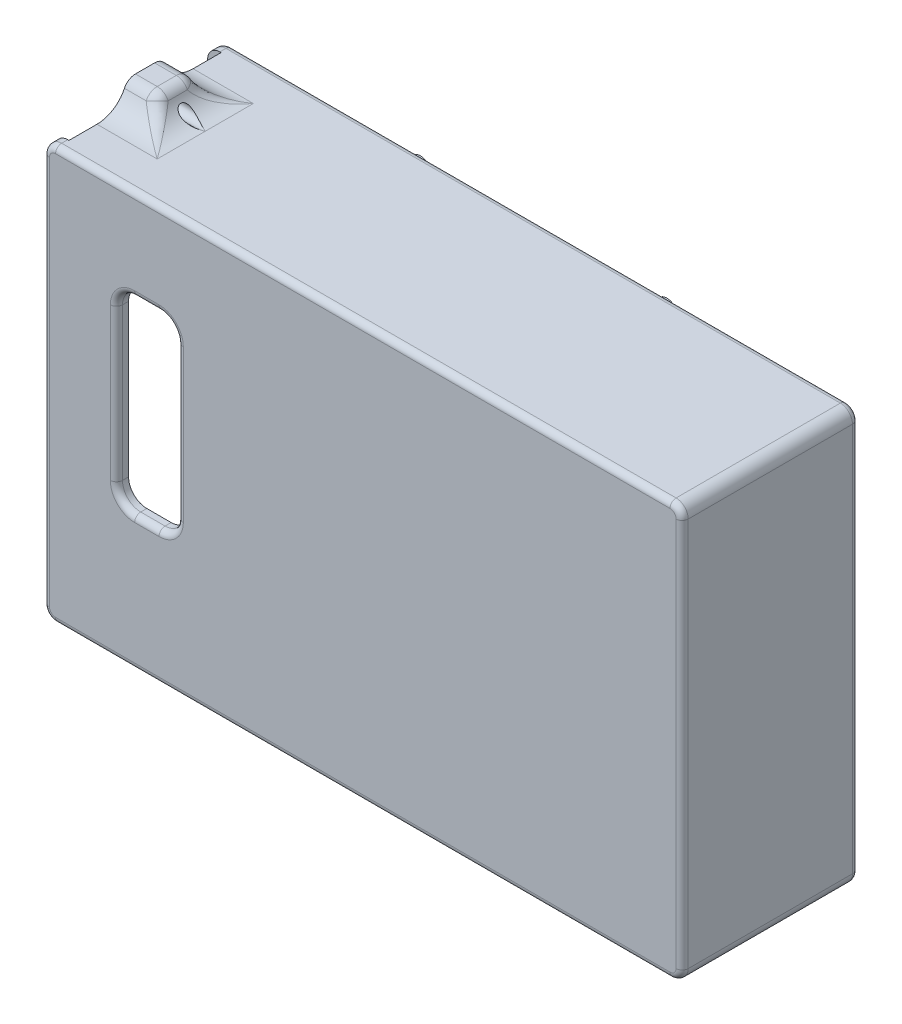
SolidWorks part; units mm, degrees
ref_plane "Front Plane" through (0, 0, 0) normal (0, 0, 1) x (1, 0, 0)
ref_plane "Top Plane" through (0, 0, 0) normal (0, 1, 0) x (1, 0, 0)
ref_plane "Right Plane" through (0, 0, 0) normal (1, 0, 0) x (0, 0, -1)
sketch "Sketch1" plane through (0, 0, 0) normal (0, 0, 1) x (1, 0, 0)
  line L0 (0, 0) -> (0, 68)
  line L1 (0, -55) -> (0, 55) construction
  line L2 (0, 68) -> (105, 68)
  line L3 (105, 68) -> (105, 0)
  line L4 (105, 0) -> (0, 0)
extrude "Boss-Extrude1" add sketch "Sketch1" along normal blind 29
sketch "Sketch2" plane through (0, 0, 0) normal (-1, 0, 0) x (0, 0, 1)
  line L8 (2, 66) -> (2, 2)
  line L9 (2, 2) -> (27, 2)
  line L10 (27, 2) -> (27, 66)
  line L11 (27, 66) -> (2, 66)
  line L12 (2, 66) -> (2, 2)
  line L13 (2, 2) -> (27, 2)
  line L14 (27, 2) -> (27, 66)
  line L15 (27, 66) -> (2, 66)
  dimension "D1" = 2
extrude "Cut-Extrude1" cut sketch "Sketch2" against normal offset from surface (103 mm away) 2 up to face at (105, 34, 14.5)
sketch "Sketch3" plane through (0, 0, 29) normal (0, 0, 1) x (1, 0, 0)
  line L0 (0, 68) -> (0, 66) construction
  line L1 (0, -15.95) -> (0, 15.95) construction
  line L2 (0, 66) -> (112.9095, 66) construction
  line L3 (0, 0) -> (0, 2) construction
  line L4 (0, 2) -> (50000, 2) construction
  line L5 (0, 0) -> (2, 0) construction
  line L6 (15.95, 0) -> (-15.95, 0) construction
  line L7 (2, 0) -> (2, 50000) construction
  line L8 (105, 68) -> (103, 68) construction
  line L9 (105, 68) -> (0, 68) construction
  line L10 (103, 68) -> (103, 50068) construction
  line L12 (12, 66) -> (12, 50066) construction
  line L13 (15, 22) -> (19, 22)
  line L14 (22, 25) -> (22, 50)
  line L15 (19, 53) -> (15, 53)
  line L16 (12, 50) -> (12, 25)
  arc A0 (22, 50) -> (19, 53) centre (19, 50) ccw
  arc A1 (19, 22) -> (22, 25) centre (19, 25) ccw
  arc A2 (15, 22) -> (12, 25) centre (15, 25) cw
  arc A3 (12, 50) -> (15, 53) centre (15, 50) cw
  point P36 (12, 22)
  point P39 (12, 53)
  dimension "D1" = 3
  dimension "D2" = 3
  dimension "D3" = 3
  dimension "D4" = 3
extrude "Cut-Extrude2" cut sketch "Sketch3" against normal blind 2
fillet "Fillet1" radius 2 8 edges at (103, 34, 27) (103, 2, 14.5) (103, 34, 2) (103, 66, 14.5) (51.5, 2, 27) (51.5, 2, 2) (51.5, 66, 27) (51.5, 66, 2)
sketch "Sketch4" plane through (0, 0, 0) normal (0, 0, -1) x (-1, 0, 0)
  line L0 (0, 0) -> (0, 2) construction
  line L1 (0, 32.45) -> (0, -32.45) construction
  line L2 (0, 2) -> (-2, 2) construction
  line L3 (-2, 2) -> (-2, 50002) construction
  line L4 (-2, 2) -> (-12, 2) construction
  line L5 (-12, 2) -> (-12, 22) construction
  line L8 (-12, 22) -> (-12, 20)
  line L9 (-12, 20) -> (-77, 20)
  line L10 (-77, 20) -> (-77, 23)
  line L11 (-77, 23) -> (-12, 23)
  line L12 (-12, 23) -> (-12, 22)
sketch "Sketch5" plane through (0, 0, 0) normal (0, 0, -1) x (-1, 0, 0)
  circle A0 centre (-9.5, 19) radius 1
  circle A1 centre (-9.5, 24) radius 1
  circle A2 centre (-79.5, 19) radius 1
  circle A3 centre (-79.5, 24) radius 1
extrude "Cut-Extrude3" cut sketch "Sketch5" against normal blind 10
sketch "Sketch6" plane through (0, 0, 0) normal (0, 0, -1) x (-1, 0, 0)
  line L0 (0, 68) -> (-30, 68) construction
  line L1 (-105, 68) -> (0, 68) construction
  line L2 (-30, 68) -> (-30, 63) construction
  line L3 (-30, 63) -> (-70.5, 63) construction
  line L4 (-70.5, 63) -> (-70.5, 47.7) construction
  line L5 (-70.5, 47.7) -> (-30, 47.7) construction
  line L6 (-30, 47.7) -> (-30, 63) construction
  circle A0 centre (-30, 63) radius 0.7
  circle A1 centre (-30, 47.7) radius 0.7
  circle A2 centre (-70.5, 63) radius 0.7
  circle A3 centre (-70.5, 47.7) radius 0.7
extrude "Cut-Extrude4" cut sketch "Sketch6" against normal blind 10
sketch "Sketch7" plane through (0, 0, 0) normal (0, 0, -1) x (-1, 0, 0)
  circle A0 centre (-70.5, 63) radius 0.7
  circle A1 centre (-70.5, 63) radius 1.7
  circle A2 centre (-70.5, 47.7) radius 0.7
  circle A3 centre (-70.5, 47.7) radius 1.7
  circle A4 centre (-30, 63) radius 0.7
  circle A5 centre (-30, 63) radius 1.7
  circle A6 centre (-30, 47.7) radius 0.7
  circle A7 centre (-30, 47.7) radius 1.7
extrude "Boss-Extrude2" add sketch "Sketch7" along normal blind 3
sketch "Sketch8" plane through (0, 0, 0) normal (-1, 0, 0) x (0, 0, 1)
  line L0 (2, 64) -> (2, 68)
  line L1 (29, 68) -> (0, 68) construction
  line L2 (2, 68) -> (26.9969, 68)
  line L3 (26.9969, 68) -> (26.9969, 0)
  line L4 (29, 0) -> (0, 0) construction
  line L5 (26.9969, 0) -> (2, 0)
  line L6 (2, 0) -> (2, 64)
extrude "Cut-Extrude5" cut sketch "Sketch8" against normal blind 2.2
sketch "Sketch9" plane through (2.2, 0, 0) normal (-1, 0, 0) x (0, 0, 1)
  line L0 (14.4984, 68) -> (11.4984, 68)
  line L1 (26.9969, 68) -> (2, 68) construction
  line L2 (11.4984, 68) -> (11.4984, 72)
  line L3 (11.4984, 72) -> (17.4984, 72)
  line L4 (17.4984, 72) -> (17.4984, 68)
  line L5 (17.4984, 68) -> (14.4984, 68)
  line L6 (29, 34) -> (50029, 34) construction
  line L7 (29, 68) -> (29, 0) construction
  line L8 (17.4984, 0) -> (14.4984, 0)
  line L9 (17.4984, -4) -> (17.4984, 0)
  line L10 (11.4984, -4) -> (17.4984, -4)
  line L11 (11.4984, 0) -> (11.4984, -4)
  line L12 (14.4984, 0) -> (11.4984, 0)
  point P11 (29, 34)
extrude "Boss-Extrude3" add sketch "Sketch9" against normal blind 5
fillet "Fillet2" radius 5 6 edges at (4.7, 68, 11.4984) (4.7, 68, 17.4984) (7.2, 68, 14.4984) (4.7, 0, 11.4984) (4.7, 0, 17.4984) (7.2, 0, 14.4984)
sketch "Sketch10" plane through (2.2, 0, 0) normal (-1, 0, 0) x (0, 0, 1)
  line L0 (14.4984, 72) -> (14.5, 66) construction
  line L1 (17.4984, 72) -> (11.4984, 72) construction
  line L2 (25, 66) -> (4, 66) construction
  line L3 (14.4984, -4) -> (14.5, 2) construction
  line L4 (11.4984, -4) -> (17.4984, -4) construction
  line L5 (4, 2) -> (25, 2) construction
  circle A0 centre (14.4992, -1) radius 1
  circle A1 centre (14.4992, 69) radius 1
extrude "Cut-Extrude6" cut sketch "Sketch10" against normal through all
fillet "Fillet3" radius 2 10 edges at (8.9367, -1.127, 9.7617) (7.2, -4, 14.4984) (8.9367, -1.127, 19.2351) (7.2, 72, 14.4984) (8.9367, 69.127, 9.7617) (8.9367, 69.127, 19.2351) (4.7, 72, 11.4984) (4.7, 72, 17.4984) (4.7, -4, 11.4984) (4.7, -4, 17.4984)
fillet "Fillet4" radius 2 4 edges at (0, 68, 1) (0, 68, 27.9984) (0, 0, 1) (0, 0, 27.9984)
fillet "Fillet5" radius 1 20 edges at (53.5, 68, 0) (0.5858, 67.4142, 0) (0, 34, 0) (0.5858, 0.5858, 0) (105, 34, 29) (53.5, 0, 29) (0.5858, 0.5858, 29) (0, 34, 29) (0.5858, 67.4142, 29) (53.5, 68, 29) (12.8787, 52.1213, 29) (12, 37.5, 29) (12.8787, 22.8787, 29) (17, 22, 29) (21.1213, 22.8787, 29) (22, 37.5, 29) (21.1213, 52.1213, 29) (17, 53, 29) (105, 34, 0) (53.5, 0, 0)
sketch "Sketch11" plane through (0, 0, 0) normal (0, 0, -1) x (-1, 0, 0)
  circle A0 centre (-2.1213, 2.1213) radius 1
  circle A1 centre (-2.1213, 65.8787) radius 1
  circle A2 centre (-102.8787, 65.8787) radius 1
  circle A3 centre (-102.8787, 2.1213) radius 1
extrude "Cut-Extrude7" cut sketch "Sketch11" against normal blind 2
fillet "Fillet6" radius 2 6 edges at (104.7071, 0.2929, 0.2929) (104.7071, 0.2929, 28.7071) (104.7071, 67.7071, 0.2929) (104.7071, 67.7071, 28.7071) (105, 68, 14.5) (105, 0, 14.5)
